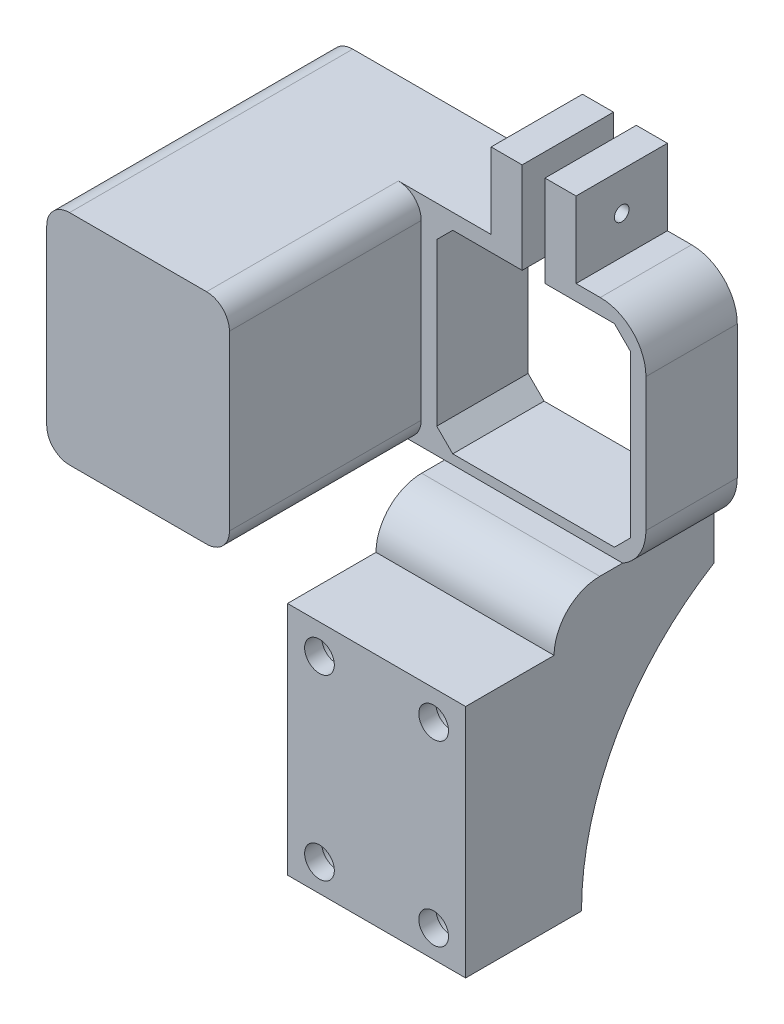
SolidWorks part; units mm, degrees
ref_plane "Front Plane" through (0, 0, 0) normal (0, 0, 1) x (1, 0, 0)
ref_plane "Top Plane" through (0, 0, 0) normal (0, 1, 0) x (1, 0, 0)
ref_plane "Right Plane" through (0, 0, 0) normal (1, 0, 0) x (0, 0, -1)
sketch "Sketch1" plane through (0, 0, 0) normal (0, 0, 1) x (1, 0, 0)
  line L1 (-21.2, -21.2) -> (21.2, -21.2)
  line L2 (-21.2, -21.2) -> (-21.2, 21.2)
  line L3 (-21.2, 21.2) -> (21.2, 21.2)
  line L4 (21.2, -21.2) -> (21.2, 21.2)
  line L5 (-21.2, -21.2) -> (21.2, 21.2) construction
  line L6 (-21.2, 21.2) -> (21.2, -21.2) construction
  line L7 (-24.6, -24.6) -> (24.6, -24.6)
  line L8 (-24.6, -24.6) -> (-24.6, 24.6)
  line L9 (-24.6, 24.6) -> (24.6, 24.6)
  line L10 (24.6, -24.6) -> (24.6, 24.6)
  line L11 (-24.6, -24.6) -> (24.6, 24.6) construction
  line L12 (-24.6, 24.6) -> (24.6, -24.6) construction
  point P0 (0, 0)
  point P5 (0, 0)
  dimension "D1" = 42.4
  dimension "D2" = 42.4
  dimension "D3" = 49.2
  dimension "D4" = 49.2
extrude "Boss-Extrude1" add sketch "Sketch1" along normal mid plane 20
chamfer "Chamfer1" distance 3.5 angle 45 4 edges at (21.2, -21.2, 0) (-21.2, -21.2, 0) (-21.2, 21.2, 0) (21.2, 21.2, 0)
fillet "Fillet1" radius 10 4 edges at (24.6, -24.6, 0) (-24.6, -24.6, 0) (-24.6, 24.6, 0) (24.6, 24.6, 0)
sketch "Sketch2" plane through (0, 0, 10) normal (0, 0, 1) x (1, 0, 0)
  line L5 (17.7, 21.2) -> (-17.7, 21.2) construction
  line L11 (-9.3, 17.8) -> (9.3, 17.8)
  line L12 (-9.3, 17.8) -> (-9.3, 24.6)
  line L17 (-9.3, 24.6) -> (9.3, 24.6)
  line L18 (9.3, 17.8) -> (9.3, 24.6)
  line L23 (-9.3, 17.8) -> (9.3, 24.6) construction
  line L24 (-9.3, 24.6) -> (9.3, 17.8) construction
  point P0 (0, 21.2)
  dimension "D1" = 6.8
  dimension "D2" = 18.6
extrude "Cut-Extrude1" cut sketch "Sketch2" against normal up to next
sketch "Sketch4" plane through (0, 21.2, 0) normal (0, -1, 0) x (1, 0, 0)
  line L1 (-9.3, -10) -> (-2.5, -10)
  line L2 (-9.3, -10) -> (-9.3, 10)
  line L3 (-9.3, 10) -> (-2.5, 10)
  line L4 (-2.5, -10) -> (-2.5, 10)
  line L5 (-17.7, 10) -> (17.7, 10) construction
  line L7 (9.3, -10) -> (2.5, -10)
  line L8 (9.3, -10) -> (9.3, 10)
  line L9 (9.3, 10) -> (2.5, 10)
  line L10 (2.5, -10) -> (2.5, 10)
  dimension "D1" = 20
  dimension "D2" = 6.8
  dimension "D3" = 20
  dimension "D4" = 6.8
extrude "Boss-Extrude2" add sketch "Sketch4" against normal blind 20
sketch "Sketch5" plane through (9.3, 0, 0) normal (1, 0, 0) x (0, 0, -1)
  circle A0 centre (0, 32.9) radius 1.6
  dimension "D1" = 3.2
extrude "Cut-Extrude2" cut sketch "Sketch5" against normal through all
sketch "Sketch7" plane through (0, 0, 0) normal (0, 0, 1) x (1, 0, 0)
  line L0 (0, 9.494) -> (0, -58.694) construction
  line L6 (-19.5, -24.6) -> (-19.5, -84.8)
  line L7 (-19.5, -84.8) -> (19.5, -84.8)
  line L8 (19.5, -84.8) -> (19.5, -24.6)
  line L10 (-19.5, -24.6) -> (-19.5, -23.3172)
  line L11 (-19.5, -23.3172) -> (19.5, -23.2738)
  line L12 (19.5, -23.2738) -> (19.5, -24.6)
  arc A1 (-24.6, -14.6) -> (-14.6, -24.6) centre (-14.6, -14.6) ccw construction
  dimension "D1" = 39
  dimension "D3" = 60.2
extrude "Boss-Extrude3" add sketch "Sketch7" along normal blind 25
sketch "Sketch8" plane through (0, 0, 0) normal (0, 0, -1) x (-1, 0, 0)
  line L3 (-19.5, -23.3172) -> (19.5, -23.3172)
  line L4 (-19.5, -23.3172) -> (-19.5, -33.3172)
  line L5 (-19.5, -33.3172) -> (19.5, -33.3172)
  line L6 (19.5, -23.3172) -> (19.5, -33.3172)
  line L7 (19.5, -23.3172) -> (19.5, -84.8) construction
  arc A1 (-24.6, -14.6) -> (-14.6, -24.6) centre (-14.6, -14.6) ccw construction
  dimension "D1" = 10
  dimension "D2" = 39
extrude "Boss-Extrude4" add sketch "Sketch8" along normal blind 10
sketch "Sketch9" plane through (0, 0, 25) normal (0, 0, 1) x (1, 0, 0)
  line L1 (-19.5, -84.8) -> (19.5, -84.8) construction
  line L2 (-19.5, -84.8) -> (-19.5, -33.8) construction
  line L3 (-19.5, -33.8) -> (19.5, -33.8) construction
  line L4 (19.5, -84.8) -> (19.5, -33.8) construction
  line L5 (19.5, -84.8) -> (19.5, -23.2738) construction
  dimension "D1" = 51
  dimension "D2" = 39
fillet "Fillet3" radius 10 1 edges at (0, -23.2955, 25)
sketch "Sketch10" plane through (-19.5, 0, 0) normal (-1, 0, 0) x (0, 0, 1)
  line L0 (0, -33.3172) -> (25, -33.3172) construction
  line L1 (25, -84.8) -> (25, -33.8) construction
  line L7 (0, -84.8) -> (19, -84.8)
  line L8 (0, -84.8) -> (0, -33.3172)
  line L9 (0, -33.3172) -> (19, -33.3172)
  line L10 (19, -84.8) -> (19, -33.3172)
  dimension "D1" = 51.4828
  dimension "D2" = 19
  dimension "D3" = 25
extrude "Cut-Extrude3" cut sketch "Sketch10" against normal up to next
fillet "Fillet4" radius 60 1 edges at (0, -33.3172, 19)
sketch "Sketch11" plane through (0, 0, 25) normal (0, 0, 1) x (1, 0, 0)
  line L0 (-19.5, -84.8) -> (-19.5, -33.8) construction
  line L1 (-19.5, -33.8) -> (19.5, -33.8) construction
  line L2 (19.5, -84.8) -> (19.5, -33.8) construction
  line L3 (-19.5, -84.8) -> (19.5, -84.8) construction
  circle A0 centre (-12.5, -39.8) radius 3.25
  circle A1 centre (12.5, -39.8) radius 3.25
  circle A2 centre (-12.5, -78.8) radius 3.25
  circle A3 centre (12.5, -78.8) radius 3.25
  dimension "D1" = 6.5
  dimension "D2" = 7
  dimension "D3" = 6
  dimension "D4" = 7
  dimension "D5" = 6
extrude "Cut-Extrude4" cut sketch "Sketch11" against normal through all
sketch "Sketch15" plane through (0, 0, -10) normal (0, 0, -1) x (-1, 0, 0)
  circle A0 centre (-12.5, -39.8) radius 4.5
  circle A1 centre (12.5, -39.8) radius 4.5
  dimension "D1" = 9
  dimension "D2" = 9
extrude "Cut-Extrude6" cut sketch "Sketch15" against normal blind 31.25
sketch "Sketch16" plane through (0, 0, -10) normal (0, 0, -1) x (-1, 0, 0)
  circle A0 centre (-12.5, -78.8) radius 4.5
  circle A1 centre (12.5, -78.8) radius 4.5
  dimension "D1" = 9
  dimension "D2" = 9
extrude "Cut-Extrude7" cut sketch "Sketch16" against normal blind 31.25
sketch "Sketch17" plane through (0, 0, 25) normal (0, 0, 1) x (1, 0, 0)
  line L4 (19.5, -84.8) -> (19.5, -33.2738)
  line L5 (19.5, -33.2738) -> (-19.5, -33.3172)
  line L6 (-19.5, -33.3172) -> (-19.5, -84.8)
  line L7 (-19.5, -84.8) -> (19.5, -84.8)
  line L8 (19.5, -84.8) -> (19.5, -33.2738)
  line L9 (19.5, -33.2738) -> (-19.5, -33.3172)
  line L10 (-19.5, -33.3172) -> (-19.5, -84.8)
  line L11 (-19.5, -84.8) -> (19.5, -84.8)
  circle A0 centre (-12.5, -78.8) radius 3.25 construction
  circle A1 centre (12.5, -78.8) radius 3.25 construction
  circle A2 centre (12.5, -39.8) radius 3.25 construction
  circle A3 centre (-12.5, -39.8) radius 3.25 construction
  circle A4 centre (-12.5, -78.8) radius 3.25
  circle A5 centre (12.5, -78.8) radius 3.25
  circle A6 centre (12.5, -39.8) radius 3.25
  circle A7 centre (-12.5, -39.8) radius 3.25
  dimension "D1" = 0
extrude "Boss-Extrude5" add sketch "Sketch17" along normal blind 19.38
sketch "Sketch18" plane through (0, 0, 21.25) normal (0, 0, -1) x (-1, 0, 0)
  circle A0 centre (12.5, -78.8) radius 4.5 construction
  circle A1 centre (-12.5, -78.8) radius 4.5 construction
  circle A2 centre (12.5, -39.8) radius 4.5 construction
  circle A3 centre (-12.5, -39.8) radius 4.5 construction
  circle A4 centre (12.5, -78.8) radius 4.5
  circle A5 centre (-12.5, -78.8) radius 4.5
  circle A6 centre (12.5, -39.8) radius 4.5
  circle A7 centre (-12.5, -39.8) radius 4.5
extrude "Cut-Extrude8" cut sketch "Sketch18" against normal blind 19.38
sketch "Sketch20" plane through (0, 0, 10) normal (0, 0, 1) x (1, 0, 0)
  line L0 (14.6, 24.6) -> (64.6, 24.6)
  line L1 (19.5, -23.2738) -> (19.5765, -23.2738)
  line L2 (64.6, 24.6) -> (64.6, -23.2738)
  line L3 (-9.3, 41.2) -> (-2.5, 41.2)
  line L5 (-2.5, 41.2) -> (-2.5, 21.2)
  line L7 (-2.5, 21.2) -> (-17.7, 21.2)
  line L9 (-17.7, 21.2) -> (-21.2, 17.7)
  line L11 (-21.2, 17.7) -> (-21.2, -17.7)
  line L13 (-21.2, -17.7) -> (-17.7, -21.2)
  line L15 (-17.7, -21.2) -> (17.7, -21.2)
  line L17 (17.7, -21.2) -> (21.2, -17.7)
  line L19 (21.2, -17.7) -> (21.2, 17.7)
  line L21 (21.2, 17.7) -> (17.7, 21.2)
  line L23 (17.7, 21.2) -> (2.5, 21.2)
  line L25 (2.5, 21.2) -> (2.5, 41.2)
  line L27 (2.5, 41.2) -> (9.3, 41.2)
  line L29 (9.3, 41.2) -> (9.3, 24.6)
  line L31 (9.3, 24.6) -> (14.6, 24.6)
  line L33 (24.6, 14.6) -> (24.6, -14.6)
  line L35 (19.5, -23.3172) -> (19.5, -33.3172)
  line L37 (19.5, -33.3172) -> (19.5, -84.6884)
  line L39 (19.5, -84.6884) -> (19.5, -84.8)
  line L40 (19.5, -84.6884) -> (19.5, -84.8)
  line L41 (19.5, -84.8) -> (-19.5, -84.8)
  line L43 (-19.5, -84.8) -> (-19.5, -84.6884)
  line L44 (-19.5, -84.8) -> (-19.5, -84.6884)
  line L45 (-19.5, -84.6884) -> (-19.5, -33.3172)
  line L47 (-19.5, -33.3172) -> (-19.5, -23.3172)
  line L49 (-24.6, -14.6) -> (-24.6, 14.6)
  line L51 (-14.6, 24.6) -> (-9.3, 24.6)
  line L53 (-9.3, 24.6) -> (-9.3, 41.2)
  line L55 (24.6, 14.6) -> (24.6, -14.6)
  line L56 (64.6, -23.2738) -> (19.5, -23.2738)
  arc A0 (24.6, 14.6) -> (14.6, 24.6) centre (14.6, 14.6) ccw
  arc A2 (19.5, -23.3172) -> (24.6, -14.6) centre (14.6, -14.6) ccw
  arc A3 (19.5, -23.3172) -> (19.5765, -23.2738) centre (14.6, -14.6) ccw
  arc A4 (-24.6, -14.6) -> (-19.5, -23.3172) centre (-14.6, -14.6) ccw
  arc A6 (-14.6, 24.6) -> (-24.6, 14.6) centre (-14.6, 14.6) ccw
  arc A9 (14.6, 24.6) -> (24.6, 14.6) centre (14.6, 14.6) cw
  arc A10 (24.6, -14.6) -> (19.5, -23.3172) centre (14.6, -14.6) cw
  spline S0 degree 3 poles (19.5, -23.3172) (19.521, -23.3054) (19.5439, -23.2909) (19.5689, -23.2738) knots 0.614797 0.614797 0.614797 0.614797 0.632326 0.632326 0.632326 0.632326
  arc M32 (19.5, -23.3172) -> (24.6, -14.6) centre (14.6, -14.6) ccw
  line M33 (24.6, -14.6) -> (24.6, 14.6)
  arc M34 (24.6, 14.6) -> (14.6, 24.6) centre (14.6, 14.6) ccw
  dimension "D1" = 50
extrude "Boss-Extrude6" add sketch "Sketch20" against normal blind 20 contours L56 L2 L0 M34 M33 M32 region at (44.2161, 0.7599, 10)
fillet "Fillet6" radius 5 2 edges at (64.6, -23.2738, 0) (64.6, 24.6, 0)
sketch "Sketch21" plane through (0, 0, 10) normal (0, 0, 1) x (1, 0, 0)
  line L0 (24.6, 24.6) -> (24.6, -23.2738)
  line L1 (59.6, 24.6) -> (9.3, 24.6) construction
  line L2 (59.6, -23.2738) -> (19.5765, -23.2738) construction
  line L3 (24.6, -23.2738) -> (59.6, -23.2738)
  line L4 (64.6, -18.2738) -> (64.6, 19.6)
  line L5 (59.6, 24.6) -> (24.6, 24.6)
  line L7 (21.2, -17.7) -> (21.2, 17.7) construction
  arc A0 (59.6, -23.2738) -> (64.6, -18.2738) centre (59.6, -18.2738) ccw
  arc A1 (64.6, 19.6) -> (59.6, 24.6) centre (59.6, 19.6) ccw
  arc A2 (64.6, 19.6) -> (59.6, 24.6) centre (59.6, 19.6) ccw construction
  dimension "D1" = 3.4
extrude "Boss-Extrude7" add sketch "Sketch21" along normal blind 42
fillet "Fillet7" radius 5 2 edges at (24.6, -23.2738, 31) (24.6, 24.6, 31)
mirror "Mirror1" about plane through (-24.6, -24.6, 10) normal (1, 0, 0) of bodies 115
delete or keep bodies "Body-Delete/Keep 1" type delete bodies bodies 115
